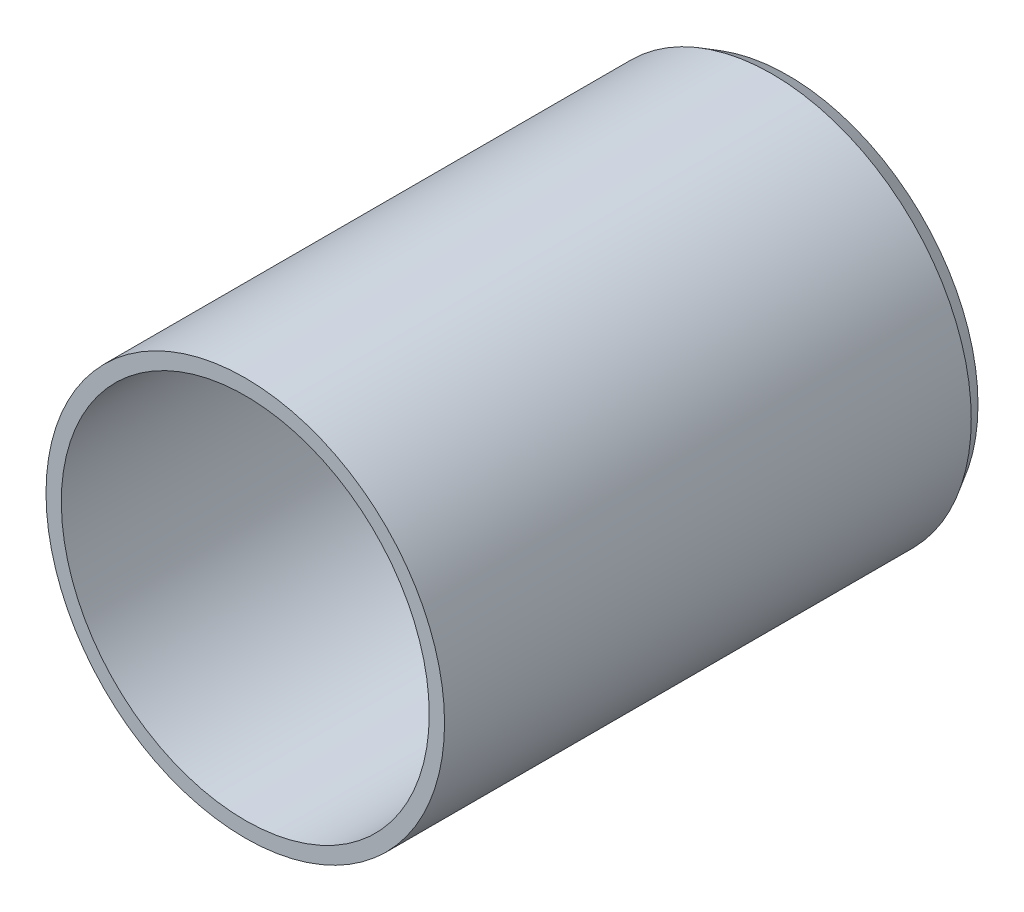
SolidWorks part; units mm, degrees
ref_plane "Front Plane" through (0, 0, 0) normal (1, 0, 0) x (0, 1, 0)
ref_plane "Top Plane" through (0, 0, 0) normal (0, 0, 1) x (0, 1, 0)
ref_plane "Right Plane" through (0, 0, 0) normal (0, 1, 0) x (-1, 0, 0)
sketch "Sketch1" plane through (0, 0, 0) normal (0, 1, 0) x (-1, 0, 0)
  line L1 (19.25, 8) -> (16.5, 9.5)
  line L2 (16.5, 9.5) -> (16.5, 20)
  line L3 (16.5, 20) -> (0, 20) construction
  line L4 (0, 20) -> (0, 0) construction
  line L5 (0, 0) -> (19.5, 0) construction
  line L8 (65, 0) -> (19.5, 0) construction
  line L9 (65, 0) -> (65, 2)
  line L10 (65, 2) -> (22, 2)
  line L11 (22, 2) -> (19.5, 20)
  line L12 (19.5, 20) -> (16.5, 20)
  line L13 (65, 0) -> (65, -5)
  line L14 (65, -5) -> (19.6562, -5)
  line L15 (19.25, 8) -> (19.6562, -5)
  point P13 (0, 0)
  dimension "D1" = 19.5
  dimension "D2" = 8
  dimension "D3" = 19.25
  dimension "D4" = 16.5
  dimension "D5" = 9.5
  dimension "D6" = 20
  dimension "D7" = 16.5
  dimension "D8" = 5
  dimension "D9" = 2
  dimension "D10" = 22
  dimension "D11" = 19.5
  dimension "D12" = 65
revolve "Revolve1" add sketch "Sketch1" angle 360 about L4
sketch "ring-1mm" plane through (0, 0, 2) normal (0, 0, 1) x (1, 0, 0)
  circle A0 centre (0, 0) radius 60
  circle A1 centre (0, 0) radius 65
  circle A2 centre (0, 0) radius 65
  dimension "D1" = 0
  dimension "D2" = 5
extrude "Boss-Extrude1" add sketch "ring-1mm" along normal blind 170
sketch "Sketch3-base-openings" plane through (0, 0, 2) normal (0, 0, 1) x (1, 0, 0)
  line L0 (0, 0) -> (60, 0) construction
  line L1 (0, 0) -> (56.3816, 20.5212) construction
  line L4 (22.4742, 8.1799) -> (54.4698, 19.8254)
  line L6 (22.4742, -8.1799) -> (54.4698, -19.8254)
  circle A5 centre (0, 0) radius 60 construction
  arc A29 (54.4698, 19.8254) -> (57.0557, 18.5648) centre (55.1538, 17.946) cw
  circle A30 centre (0, 0) radius 60
  arc A31 (57.0557, -18.5648) -> (57.0557, 18.5648) centre (0, 0) ccw
  arc A33 (21.2284, 5.7755) -> (22.4742, 8.1799) centre (23.1582, 6.3005) cw
  circle A34 centre (0, 0) radius 22
  arc A35 (21.2284, -5.7755) -> (21.2284, 5.7755) centre (0, 0) ccw
  arc A36 (54.4698, -19.8254) -> (57.0557, -18.5648) centre (55.1538, -17.946) ccw
  arc A37 (21.2284, -5.7755) -> (22.4742, -8.1799) centre (23.1582, -6.3005) ccw
  point P20 (56.3816, 20.5212)
  point P26 (20.6732, 7.5244)
  point P84 (0, 0)
  dimension "D2" = 0
  dimension "D4" = 2
  dimension "D5" = 2
  dimension "D1" = 20
  dimension "D3" = 0
extrude "Cut-Extrude2" cut sketch "Sketch3-base-openings" against normal blind 240
pattern_circular "CirPattern1" count 6 over 360 about axis through (0, 0, 2) along (0, 0, 1) of "Cut-Extrude2"
chamfer "Chamfer1" distance 3 angle 60 1 edges at (65, 0, -5) first distance on face at (-39.2211, 0, -5)
